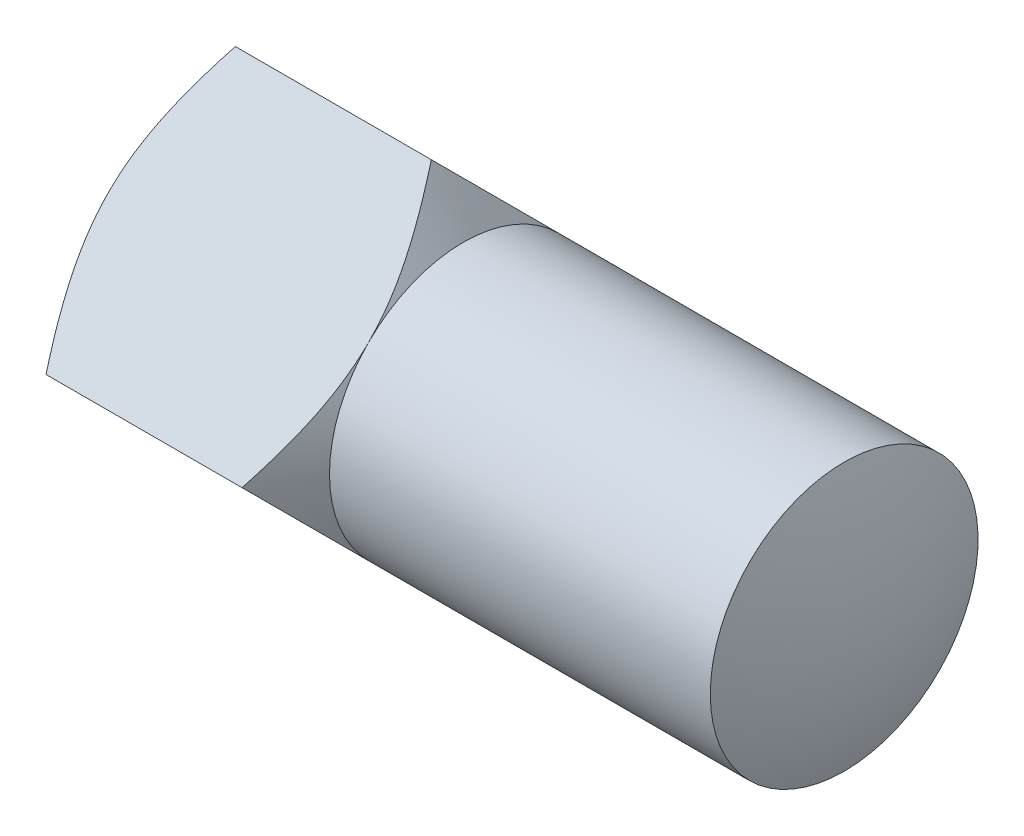
SolidWorks part; units mm, degrees
ref_plane "Front Plane" through (0, 0, 0) normal (0, 0, 1) x (1, 0, 0)
ref_plane "Top Plane" through (0, 0, 0) normal (0, 1, 0) x (1, 0, 0)
ref_plane "Right Plane" through (0, 0, 0) normal (1, 0, 0) x (0, 0, -1)
sketch "BaseHeadSke" plane through (0, 0, 0) normal (1, 0, 0) x (0, 0, -1)
  line L0 (0, 0) -> (14.1701, 0) construction
  line L1 (0, 0) -> (0, 11.9761) construction
  line L2 (0, 2.8284) -> (2.8284, 0)
  line L3 (0, -2.8284) -> (2.8284, 0)
  line L4 (0, 2.8284) -> (-2.8284, 0)
  line L5 (0, -2.8284) -> (-2.8284, 0)
  dimension "Width_flats" = 4
  dimension "Angle" = 45
extrude "BaseHead" add sketch "BaseHeadSke" along normal blind 4
sketch "HeadChamferSke" plane through (0, 0, 0) normal (0, 0, 1) x (1, 0, 0)
  line L0 (0, 0) -> (6.1973, 0) construction
  line L1 (2, 2.8284) -> (2, -3.5627) construction
  line L2 (4, 2.8284) -> (0, 2.8284) construction
  line L3 (0, 2.8284) -> (0, 1.9)
  line L4 (0, 2.8284) -> (0.536, 2.8284)
  line L5 (0.536, 2.8284) -> (0, 1.9)
  line L6 (0, 2.8284) -> (0, 0) construction
  line L7 (3.464, 2.8284) -> (4, 1.9)
  line L8 (4, 2.8284) -> (3.464, 2.8284)
  line L9 (4, 2.8284) -> (4, 1.9)
  dimension "Head_chamfer" = 3.8
  dimension "Angle" = 30
revolve "HeadChamfer" cut sketch "HeadChamferSke" angle 360 about L0
sketch "BodySke" plane through (0, 0, 0) normal (0, 0, 1) x (1, 0, 0)
  line L0 (0, 0) -> (13.1857, 0) construction
  line L1 (4, -1.9) -> (4, 1.9) construction
  line L2 (4, 0) -> (4, 1.9) construction
  line L3 (3.464, 2) -> (9.6307, 2)
  line L4 (10, 2) -> (10, 0) construction
  line L5 (4, 1.9) -> (4, 2) construction
  line L6 (3.464, 2) -> (3.464, 0)
  line L7 (3.464, 0) -> (10, 0)
  line L8 (9.6307, 2) -> (9.6307, -2) construction
  line L9 (10, 2) -> (9.6307, 2) construction
  line L10 (9.3, 2.6461) -> (9.3, -2) construction
  arc A0 (9.6307, 2) -> (10, 0) centre (4.4, 0) cw
  point P15 (3.464, 1.61)
  dimension "Minor_dia" = 3.22
  dimension "Advance" = 0.7
revolve "BaseBody" add sketch "BodySke" angle 360 about L0
cosmetic thread "ThreadCosmetic" [suppressed] parameters "Minor_dia"=3.22
sketch "ThdSchSke" plane through (0, 0, 0) normal (0, 0, 1) x (1, 0, 0)
  line L0 (8.9307, 2.4503) -> (8.9307, 2)
  line L1 (8.9307, 2.4503) -> (9.381, 2.4503)
  line L2 (9.381, 2.4503) -> (9.381, 2)
  line L3 (9.381, 2) -> (9.1558, 1.61)
  line L4 (9.1558, 1.61) -> (8.9307, 2)
  line L5 (0, 0) -> (11.8711, 0) construction
  line L8 (9.6307, 2) -> (3.9423, 2) construction
  dimension "D1" = 0.7
revolve "ThreadSchematic" [suppressed] cut sketch "ThdSchSke" angle 360 about L5
pattern_linear "ThdSchPat" [suppressed] count 7 of bodies 105
equation "\"Minor_dia@ThreadCosmetic\" = \"Minor_dia@BodySke\""
equation "\"D1@ThdSchSke\" = \"Advance@BodySke\""
equation "\"Advance@ThdSchPat\" = \"Advance@BodySke\""
equation "\"D1@ThdSchPat\" =  int( \"Length@BodySke\" / \"Advance@ThdSchPat\" )  - 1"
